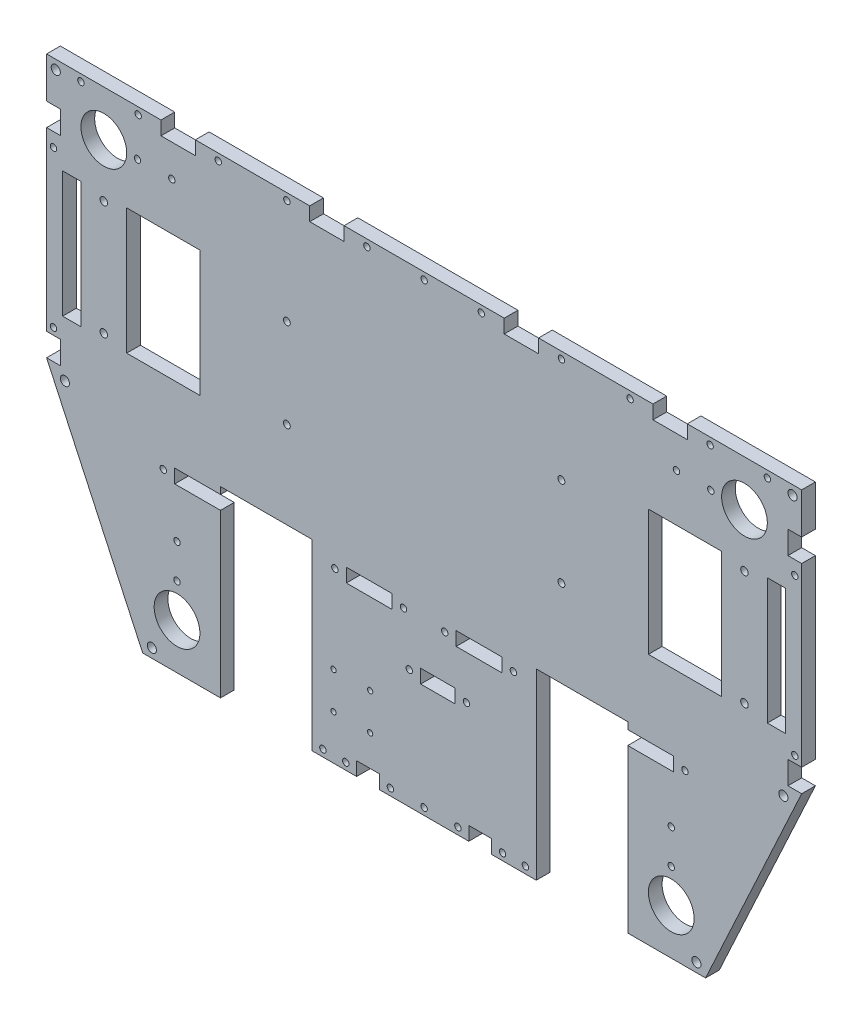
SolidWorks part; units mm, degrees
ref_plane "Plan de face" through (0, 0, 0) normal (0, 0, 1) x (1, 0, 0)
ref_plane "Plan de dessus" through (0, 0, 0) normal (0, 1, 0) x (1, 0, 0)
ref_plane "Plan de droite" through (0, 0, 0) normal (1, 0, 0) x (0, 0, -1)
sketch "Esquisse1" plane through (0, 0, 0) normal (0, 0, 1) x (1, 0, 0)
  line L0 (0, 124.9429) -> (0, -204.46) construction
  line L1 (-165, 96.73) -> (165, 96.73)
  line L2 (165, 96.73) -> (165, -18.27)
  line L3 (165, -18.27) -> (123, -109.0224)
  line L4 (123, -109.0224) -> (-123, -109.0224)
  line L5 (-211.9802, 0) -> (248.5953, 0) construction
  line L6 (-123, -109.0224) -> (-165, -18.27)
  line L7 (-165, -18.27) -> (-165, 96.73)
  line L9 (13.5, -54.0224) -> (-1.5, -54.0224)
  line L10 (13.5, -54.0224) -> (13.5, -60.0224)
  line L11 (13.5, -60.0224) -> (-1.5, -60.0224)
  line L12 (-1.5, -54.0224) -> (-1.5, -60.0224)
  circle A0 centre (-23.6, -89.5224) radius 1.15
  circle A1 centre (-23.6, -73.5224) radius 1.15
  circle A2 centre (-39.6, -89.5224) radius 1.15
  circle A3 centre (-39.6, -73.5224) radius 1.15
  dimension "D15" = 2.3
  dimension "D16" = 2.3
  dimension "D17" = 2.3
  dimension "D18" = 2.3
  dimension "D24" = 83.4
  dimension "D2" = 165
  dimension "D3" = 330
  dimension "D4" = 100
  dimension "D5" = 115
  dimension "D6" = 100
  dimension "D7" = 246
  dimension "D8" = 205.7524
  dimension "D9" = 96.73
  dimension "D10" = 115
  dimension "D11" = 6
  dimension "D12" = 15
  dimension "D13" = 49
  dimension "D14" = 109.5
  dimension "D19" = 19.5
  dimension "D20" = 16
  dimension "D21" = 16
  dimension "D22" = 16
  dimension "D23" = 16
extrude "Boss.-Extru.1" add sketch "Esquisse1" along normal blind 6
sketch "Esquisse2" plane through (0, 0, 6) normal (0, 0, 1) x (1, 0, 0)
  line L0 (-123, -109.0224) -> (123, -109.0224) construction
  line L1 (-158, 55.9776) -> (-150, 55.9776)
  line L2 (-158, 55.9776) -> (-158, 0.9776)
  line L3 (-158, 0.9776) -> (-150, 0.9776)
  line L4 (-150, 55.9776) -> (-150, 0.9776)
  line L5 (-130, 55.9776) -> (-98, 55.9776)
  line L6 (-130, 55.9776) -> (-130, 0.9776)
  line L7 (-130, 0.9776) -> (-98, 0.9776)
  line L8 (-98, 55.9776) -> (-98, 0.9776)
  line L9 (0, 145.0258) -> (0, -189.2208) construction
  line L10 (98, 55.9776) -> (98, 0.9776)
  line L11 (130, 0.9776) -> (98, 0.9776)
  line L12 (130, 55.9776) -> (130, 0.9776)
  line L13 (130, 55.9776) -> (98, 55.9776)
  line L14 (150, 55.9776) -> (150, 0.9776)
  line L15 (158, 0.9776) -> (150, 0.9776)
  line L16 (158, 55.9776) -> (158, 0.9776)
  line L17 (158, 55.9776) -> (150, 55.9776)
  line L19 (89, -109.0224) -> (89, -29.0224)
  line L20 (-49, -109.0224) -> (-89, -109.0224)
  line L21 (-49, -109.0224) -> (-49, -29.0224)
  line L22 (-49, -29.0224) -> (-89, -29.0224)
  line L23 (-89, -109.0224) -> (-89, -29.0224)
  line L24 (49, -29.0224) -> (89, -29.0224)
  line L25 (49, -109.0224) -> (49, -29.0224)
  line L26 (49, -109.0224) -> (89, -109.0224)
  line L27 (-165, 96.73) -> (-165, -18.27) construction
  line L28 (-123, -109.0224) -> (123, -109.0224) construction
  line L29 (165, -18.27) -> (165, 96.73) construction
  line L30 (165, 96.73) -> (-165, 96.73) construction
  circle A0 centre (140, 76.73) radius 10
  circle A1 centre (108, -89.0224) radius 10
  circle A2 centre (-140, 76.73) radius 10
  circle A3 centre (-108, -89.0224) radius 10
  circle A4 centre (157, -23.0224) radius 2
  circle A5 centre (119, -105.0224) radius 2
  circle A6 centre (161, 92.73) radius 2
  circle A7 centre (-161, 92.73) radius 2
  circle A8 centre (-157, -23.0224) radius 2
  circle A9 centre (-119, -105.0224) radius 2
  circle A10 centre (125.27, 76.73) radius 1.4
  circle A11 centre (110.27, 76.73) radius 1.4
  circle A12 centre (108, -74.2924) radius 1.4
  circle A13 centre (108, -59.2924) radius 1.4
  circle A14 centre (-110.27, 76.73) radius 1.4
  circle A15 centre (-125.27, 76.73) radius 1.4
  circle A16 centre (-108, -59.2924) radius 1.4
  circle A17 centre (-108, -74.2924) radius 1.4
  dimension "D16" = 20
  dimension "D17" = 20
  dimension "D18" = 15
  dimension "D19" = 20
  dimension "D20" = 25
  dimension "D21" = 20
  dimension "D24" = 8
  dimension "D15" = 4
  dimension "D25" = 4
  dimension "D28" = 4
  dimension "D29" = 4
  dimension "D30" = 2.8
  dimension "D31" = 2.8
  dimension "D34" = 2.8
  dimension "D35" = 2.8
  dimension "D2" = 8
  dimension "D3" = 20
  dimension "D4" = 32
  dimension "D5" = 98
  dimension "D6" = 55
  dimension "D7" = 55
  dimension "D8" = 110
  dimension "D9" = 110
  dimension "D10" = 40
  dimension "D11" = 80
  dimension "D12" = 76
  dimension "D13" = 98
  dimension "D14" = 7
  dimension "D22" = 4
  dimension "D23" = 4
  dimension "D26" = 24
  dimension "D27" = 4
  dimension "D32" = 14.73
  dimension "D33" = 15
  dimension "D36" = 14.73
  dimension "D37" = 15
extrude "Enlèv. mat.-Extru.1" cut sketch "Esquisse2" against normal blind 6
sketch "Esquisse3" plane through (0, 0, 0) normal (0, 0, -1) x (-1, 0, 0)
  line L0 (165, 96.73) -> (165, -18.27) construction
  line L1 (165, -18.27) -> (159, -18.27)
  line L2 (165, -18.27) -> (165, -8.27)
  line L3 (165, -8.27) -> (159, -8.27)
  line L4 (159, -18.27) -> (159, -8.27)
  line L5 (49, -109.0224) -> (-49, -109.0224) construction
  line L6 (165, 68.8526) -> (159, 68.8526)
  line L7 (165, 68.8526) -> (165, 78.8526)
  line L8 (165, 78.8526) -> (159, 78.8526)
  line L9 (159, 68.8526) -> (159, 78.8526)
  line L10 (29.5, -109.0224) -> (19.5, -109.0224)
  line L11 (29.5, -109.0224) -> (29.5, -103.0224)
  line L12 (29.5, -103.0224) -> (19.5, -103.0224)
  line L13 (19.5, -109.0224) -> (19.5, -103.0224)
  line L14 (49, -109.0224) -> (49, -29.0224) construction
  line L15 (0, -209.4812) -> (0, 177.1799) construction
  line L17 (150, 55.9776) -> (158, 55.9776) construction
  line L18 (-19.5, -109.0224) -> (-19.5, -103.0224)
  line L19 (-29.5, -103.0224) -> (-19.5, -103.0224)
  line L20 (-29.5, -109.0224) -> (-29.5, -103.0224)
  line L21 (-29.5, -109.0224) -> (-19.5, -109.0224)
  line L22 (-159, 68.8526) -> (-159, 78.8526)
  line L23 (-165, 78.8526) -> (-159, 78.8526)
  line L24 (-165, 68.8526) -> (-165, 78.8526)
  line L25 (-165, 68.8526) -> (-159, 68.8526)
  line L26 (-159, -18.27) -> (-159, -8.27)
  line L27 (-165, -8.27) -> (-159, -8.27)
  line L28 (-165, -18.27) -> (-165, -8.27)
  line L29 (-165, -18.27) -> (-159, -18.27)
  line L30 (-165, 96.73) -> (165, 96.73) construction
  line L31 (115, 96.73) -> (100, 96.73)
  line L32 (115, 96.73) -> (115, 90.73)
  line L33 (115, 90.73) -> (100, 90.73)
  line L34 (100, 96.73) -> (100, 90.73)
  line L35 (-35, 96.73) -> (-35, 90.73)
  line L36 (50, 96.73) -> (35, 96.73)
  line L37 (50, 96.73) -> (50, 90.73)
  line L38 (50, 90.73) -> (35, 90.73)
  line L39 (35, 96.73) -> (35, 90.73)
  line L40 (-50, 90.73) -> (-35, 90.73)
  line L41 (-50, 96.73) -> (-50, 90.73)
  line L42 (-50, 96.73) -> (-35, 96.73)
  line L43 (-100, 96.73) -> (-100, 90.73)
  line L44 (-115, 90.73) -> (-100, 90.73)
  line L45 (-115, 96.73) -> (-115, 90.73)
  line L46 (-115, 96.73) -> (-100, 96.73)
  dimension "D1" = 10
  dimension "D2" = 6
  dimension "D3" = 6
  dimension "D4" = 10
  dimension "D5" = 10
  dimension "D6" = 6
  dimension "D7" = 19.5
  dimension "D9" = 12.875
  dimension "D10" = 15
  dimension "D11" = 15
  dimension "D12" = 50
  dimension "D13" = 50
  dimension "D14" = 6
extrude "Enlèv. mat.-Extru.2" cut sketch "Esquisse3" against normal blind 6
sketch "Esquisse4" plane through (0, 0, 0) normal (0, 0, -1) x (-1, 0, 0)
  line L0 (159, 68.8526) -> (165, 68.8526) construction
  line L1 (13.1585, 93.73) -> (156.271, 93.73) construction
  line L2 (54.0695, -106.0224) -> (4.75, -106.0224) construction
  line L3 (49, -109.0224) -> (29.5, -109.0224) construction
  line L4 (49, -109.0224) -> (49, -29.0224) construction
  line L5 (19.5, -103.0224) -> (19.5, -109.0224) construction
  line L8 (165, 68.8526) -> (165, -8.27) construction
  line L13 (115, 90.73) -> (115, 96.73) construction
  line L14 (100, 96.73) -> (100, 90.73) construction
  line L15 (50, 90.73) -> (50, 96.73) construction
  line L16 (35, 96.73) -> (35, 90.73) construction
  line L17 (0, 142.2997) -> (0, -202.2086) construction
  line L21 (165, -8.27) -> (159, -8.27) construction
  circle A0 centre (162, -5.27) radius 1.4
  circle A1 centre (0, -106.0224) radius 1.4
  circle A2 centre (162, 62.8526) radius 1.4
  circle A3 centre (0, 93.73) radius 1.4
  circle A4 centre (-34.2497, -106.0224) radius 1.4
  circle A5 centre (-14.75, -106.0224) radius 1.4
  circle A6 centre (44.25, -106.0224) radius 1.4
  circle A7 centre (14.75, -106.0224) radius 1.4
  circle A8 centre (-44.25, -106.0224) radius 1.4
  circle A9 centre (34.2497, -106.0224) radius 1.4
  circle A10 centre (150, 93.73) radius 1.4
  circle A11 centre (125, 93.73) radius 1.4
  circle A12 centre (90, 93.73) radius 1.4
  circle A13 centre (-25, 93.73) radius 1.4
  circle A14 centre (60, 93.73) radius 1.4
  circle A15 centre (25, 93.73) radius 1.4
  circle A16 centre (-60, 93.73) radius 1.4
  circle A17 centre (-90, 93.73) radius 1.4
  circle A18 centre (-125, 93.73) radius 1.4
  circle A19 centre (-150, 93.73) radius 1.4
  circle A31 centre (-162, 62.8526) radius 1.4
  circle A33 centre (-162, -5.27) radius 1.4
  dimension "D3" = 2.8
  dimension "D11" = 2.8
  dimension "D12" = 2.8
  dimension "D13" = 2.8
  dimension "D14" = 10.0003
  dimension "D18" = 3
  dimension "D19" = 2.8
  dimension "D29" = 2.8
  dimension "D30" = 2.8
  dimension "D31" = 2.8
  dimension "D33" = 2.8
  dimension "D34" = 2.8
  dimension "D40" = 10
  dimension "D5" = 3
  dimension "D7" = 2.8
  dimension "D8" = 2.8
  dimension "D6" = 6
  dimension "D9" = 3
  dimension "D15" = 4.75
  dimension "D17" = 4.75
  dimension "D26" = 3
  dimension "D36" = 25
  dimension "D37" = 10
  dimension "D38" = 10
  dimension "D42" = 10
extrude "Enlèv. mat.-Extru.3" cut sketch "Esquisse4" against normal blind 6
sketch "Esquisse5" plane through (0, 0, 0) normal (0, 0, -1) x (-1, 0, 0)
  line L0 (89, -29.0224) -> (89, -109.0224) construction
  line L1 (89, -38.0224) -> (109, -38.0224)
  line L2 (89, -38.0224) -> (89, -32.0224)
  line L3 (89, -32.0224) -> (109, -32.0224)
  line L4 (109, -38.0224) -> (109, -32.0224)
  line L5 (0, -159.6455) -> (0, 113.5094) construction
  line L6 (34, -38.0224) -> (14, -38.0224)
  line L7 (34, -38.0224) -> (34, -32.0224)
  line L8 (34, -32.0224) -> (14, -32.0224)
  line L9 (14, -38.0224) -> (14, -32.0224)
  line L10 (49, -109.0224) -> (49, -29.0224) construction
  line L11 (-14, -38.0224) -> (-14, -32.0224)
  line L12 (-34, -32.0224) -> (-14, -32.0224)
  line L13 (-34, -38.0224) -> (-34, -32.0224)
  line L14 (-34, -38.0224) -> (-14, -38.0224)
  line L15 (-109, -38.0224) -> (-109, -32.0224)
  line L16 (-89, -32.0224) -> (-109, -32.0224)
  line L17 (-89, -38.0224) -> (-89, -32.0224)
  line L18 (-89, -38.0224) -> (-109, -38.0224)
  line L22 (49, -29.0224) -> (89, -29.0224) construction
  dimension "D1" = 20
  dimension "D2" = 20
  dimension "D3" = 15
  dimension "D4" = 6
  dimension "D5" = 6
  dimension "D6" = 3
  dimension "D7" = 3
extrude "Enlèv. mat.-Extru.4" cut sketch "Esquisse5" against normal blind 6
sketch "Esquisse6" plane through (0, 0, 0) normal (0, 0, -1) x (-1, 0, 0)
  line L0 (-159, -8.27) -> (-165, -8.27) construction
  line L1 (-165, -8.27) -> (-165, 68.8526) construction
  line L2 (0, 127.7926) -> (0, -140.3318) construction
  line L3 (-42.2546, -35.0224) -> (44.6597, -35.0224) construction
  line L4 (12.4063, -57.0224) -> (-22.6465, -57.0224) construction
  line L5 (34, -38.0224) -> (34, -32.0224) construction
  line L6 (14, -32.0224) -> (14, -38.0224) construction
  line L7 (-13.5, -60.0224) -> (-13.5, -54.0224) construction
  line L8 (1.5, -54.0224) -> (1.5, -60.0224) construction
  line L9 (109, -38.0224) -> (109, -32.0224) construction
  line L10 (113.2167, -35.0224) -> (-121.7916, -35.0224) construction
  line L13 (-60, 47.98) -> (60, 47.98) construction
  line L14 (-60, 47.98) -> (-60, 8.9803) construction
  line L15 (-60, 8.9803) -> (60, 8.9803) construction
  line L16 (60, 47.98) -> (60, 8.9803) construction
  line L17 (-35, 96.73) -> (35, 96.73) construction
  line L19 (-98, 55.9776) -> (-98, 0.9776) construction
  circle A0 centre (-140, 3.48) radius 1.65
  circle A1 centre (-140, 53.48) radius 1.65
  circle A2 centre (140, 53.48) radius 1.65
  circle A3 centre (140, 3.48) radius 1.65
  circle A4 centre (-39, -35.0224) radius 1.4
  circle A5 centre (9, -35.0224) radius 1.4
  circle A6 centre (39, -35.0224) radius 1.4
  circle A7 centre (-9, -35.0224) radius 1.4
  circle A8 centre (-18.5, -57.0224) radius 1.4
  circle A9 centre (6.5, -57.0224) radius 1.4
  circle A10 centre (114, -35.0224) radius 1.4
  circle A11 centre (-114, -35.0224) radius 1.4
  circle A12 centre (-60, 47.98) radius 1.5
  circle A13 centre (-60, 8.9803) radius 1.5
  circle A14 centre (60, 8.9803) radius 1.5
  circle A15 centre (60, 47.98) radius 1.5
  point P51 (-98, 28.4776)
  dimension "D1" = 3.3
  dimension "D2" = 3.3
  dimension "D7" = 2.8
  dimension "D8" = 2.8
  dimension "D9" = 5
  dimension "D11" = 2.8
  dimension "D12" = 2.8
  dimension "D13" = 5
  dimension "D14" = 5
  dimension "D15" = 2.8
  dimension "D16" = 5
  dimension "D17" = 48.75
  dimension "D18" = 3
  dimension "D19" = 38
  dimension "D20" = 3
  dimension "D21" = 3
  dimension "D22" = 3
  dimension "D3" = 11.75
  dimension "D4" = 25
  dimension "D5" = 25
  dimension "D6" = 50
  dimension "D10" = 5
  dimension "D23" = 120
  dimension "D24" = 38.9997
extrude "Enlèv. mat.-Extru.5" cut sketch "Esquisse6" against normal blind 6
